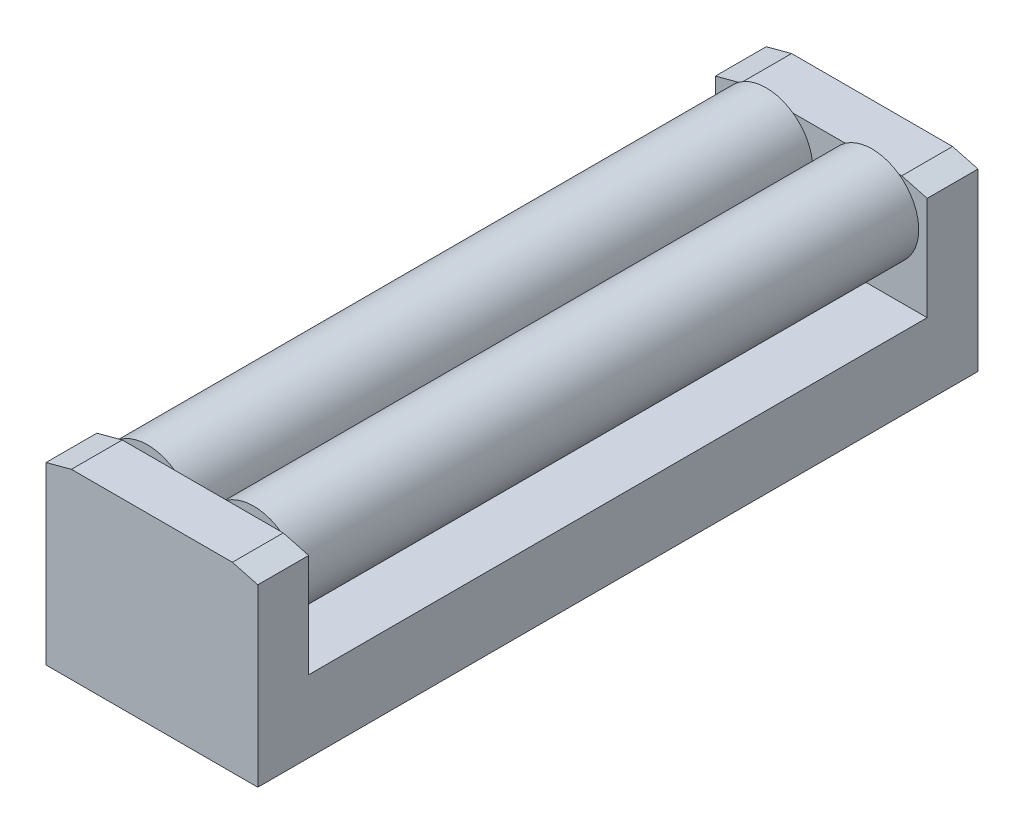
SolidWorks part; units mm, degrees
ref_plane "Frontale" through (0, 0, 0) normal (0, 0, 1) x (1, 0, 0)
ref_plane "Superiore" through (0, 0, 0) normal (0, 1, 0) x (1, 0, 0)
ref_plane "Destro" through (0, 0, 0) normal (1, 0, 0) x (0, 0, -1)
sketch "Schizzo1" plane through (0, 0, 0) normal (0, 0, 1) x (1, 0, 0)
  line L1 (0, 0) -> (25, 0)
  line L2 (0, 0) -> (0, 21.5)
  line L3 (0, 21.5) -> (25, 21.5)
  line L4 (25, 0) -> (25, 21.5)
  dimension "D1" = 25
  dimension "D2" = 21.5
extrude "Estrusione1" add sketch "Schizzo1" along normal blind 85
sketch "Schizzo6" plane through (25, 0, 0) normal (1, 0, 0) x (0, 0, -1)
  line L1 (-85, 0) -> (-85, 21.5) construction
  line L2 (-85, 0) -> (0, 0) construction
  line L9 (-79, 32.1395) -> (-6, 32.1395)
  line L10 (-79, 32.1395) -> (-79, 8.5)
  line L11 (-79, 8.5) -> (-6, 8.5)
  line L12 (-6, 32.1395) -> (-6, 8.5)
  line L13 (-317.5773, 8.5) -> (13.8875, 8.5) construction
  dimension "D1" = 6
  dimension "D2" = 8.5
  dimension "D5" = 6
extrude "Taglio-Estrusione4" cut sketch "Schizzo6" against normal blind 84
sketch "Schizzo7" plane through (0, 0, 6) normal (0, 0, 1) x (1, 0, 0)
  line L0 (-0.9369, 17) -> (39.6559, 17) construction
  line L1 (0, 21.5) -> (0, 0) construction
  line L4 (0, 0) -> (25, 0) construction
  circle A0 centre (6, 17) radius 5.5
  circle A1 centre (18.5, 17) radius 5.5
  dimension "D1" = 11
  dimension "D2" = 11
  dimension "D3" = 17
  dimension "D4" = 12.5
  dimension "D6" = 6
extrude "Estrusione4" add sketch "Schizzo7" along normal up to surface (73 mm away) up to face at (12.5, 15, 79)
chamfer "Smusso1" distance 3 angle 15 4 edges at (0, 21.5, 3) (25, 21.5, 3) (25, 21.5, 82) (0, 21.5, 82) first distance on face at (12.375, 21.5, 4.5) first distance on face at (12.375, 21.5, 80.5)
sketch "Schizzo8" plane through (0, 0, 0) normal (0, -1, 0) x (1, 0, 0)
  line L0 (12, 120.9167) -> (12, -3.7523) construction
  line L1 (25, 85) -> (25, 0) construction
  line L2 (0, 85) -> (25, 85) construction
  circle A0 centre (12, 75.5) radius 3
  circle A1 centre (12, 9.5) radius 3
  dimension "D1" = 6
  dimension "D2" = 6
  dimension "D3" = 66
  dimension "D4" = 13
  dimension "D5" = 9.5
extrude "Taglio-Estrusione5" cut sketch "Schizzo8" against normal up to surface (8.5 mm away) up to face at (12.5, 8.5, 42.5)
